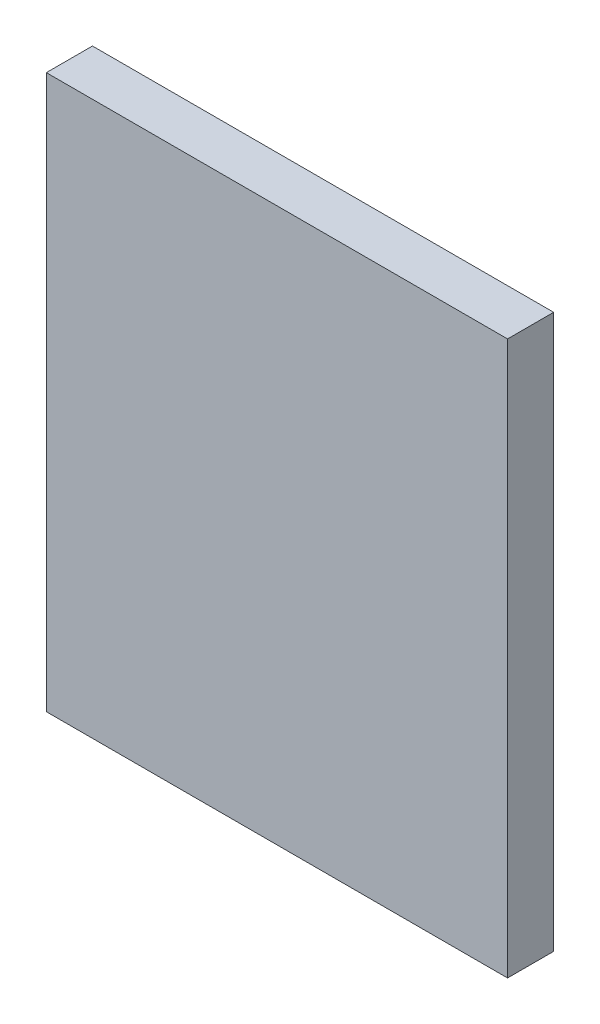
SolidWorks part; units mm, degrees
ref_plane "前视基准面" through (0, 0, 0) normal (0, 0, 1) x (1, 0, 0)
ref_plane "上视基准面" through (0, 0, 0) normal (0, 1, 0) x (1, 0, 0)
ref_plane "右视基准面" through (0, 0, 0) normal (1, 0, 0) x (0, 0, -1)
other "Configuration Table"
sketch "草图1" plane through (0, 0, 0) normal (0, 0, 1) x (1, 0, 0)
  line L0 (0, 0) -> (50, 0)
  line L1 (50, 0) -> (50, 60)
  line L2 (0, 0) -> (0, 60)
  line L3 (0, 60) -> (50, 60)
extrude "凸台-拉伸1" add sketch "草图1" along normal blind 5
